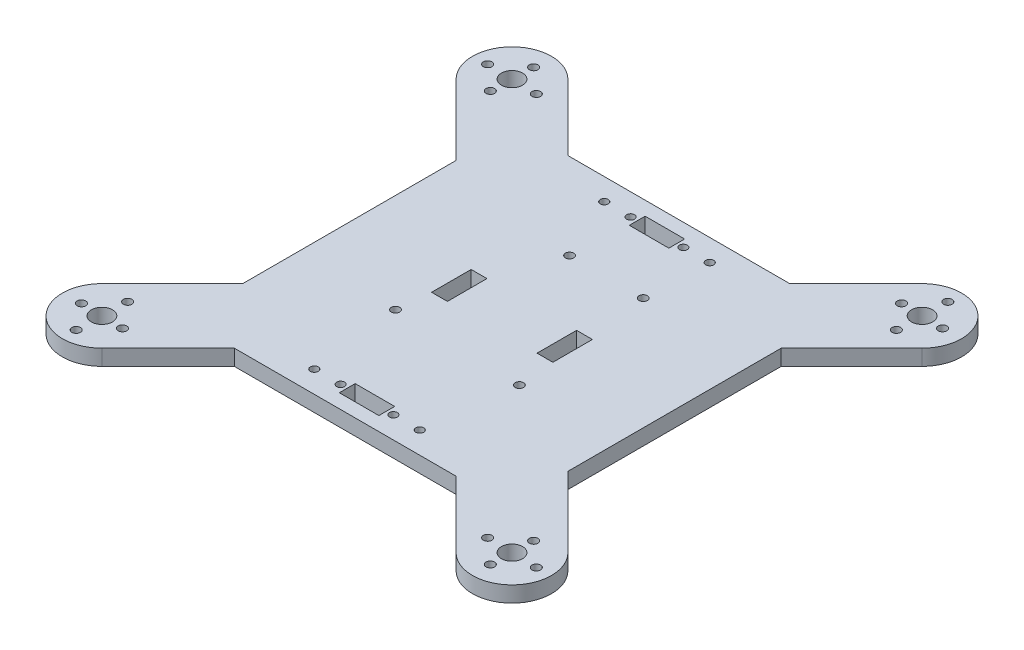
SolidWorks part; units mm, degrees
ref_plane "Front Plane" through (0, 0, 0) normal (0, 0, 1) x (1, 0, 0)
ref_plane "Top Plane" through (0, 0, 0) normal (0, 1, 0) x (1, 0, 0)
ref_plane "Right Plane" through (0, 0, 0) normal (1, 0, 0) x (0, 0, -1)
sketch "Sketch1" plane through (0, 0, 0) normal (0, 1, 0) x (1, 0, 0)
  line L0 (-67.1751, 88.3883) -> (88.3883, -67.1751)
  line L1 (-77.7817, 77.7817) -> (77.7817, 77.7817) construction
  line L2 (-77.7817, 77.7817) -> (-77.7817, -77.7817) construction
  line L3 (-77.7817, -77.7817) -> (77.7817, -77.7817) construction
  line L4 (77.7817, 77.7817) -> (77.7817, -77.7817) construction
  line L5 (-77.7817, 77.7817) -> (77.7817, -77.7817) construction
  line L6 (-77.7817, -77.7817) -> (77.7817, 77.7817) construction
  line L7 (67.1751, 88.3883) -> (-88.3883, -67.1751)
  line L8 (88.3883, 67.1751) -> (-67.1751, -88.3883)
  line L9 (-88.3883, 67.1751) -> (67.1751, -88.3883)
  line L10 (0, -1000) -> (0, 49000) construction
  line L11 (-1000, 0) -> (49000, 0) construction
  circle A0 centre (-77.7817, 77.7817) radius 15
  circle A1 centre (77.7817, 77.7817) radius 15
  circle A2 centre (-77.7817, -77.7817) radius 15
  circle A3 centre (77.7817, -77.7817) radius 15
  circle A4 centre (-77.7817, 77.7817) radius 4
  circle A5 centre (77.7817, 77.7817) radius 4
  circle A6 centre (77.7817, -77.7817) radius 4
  circle A7 centre (-77.7817, -77.7817) radius 4
  point P0 (0, 0)
  point P14 (10.6066, 10.6066)
  point P16 (10.6066, -10.6066)
  dimension "D4" = 8
  dimension "D1" = 220
  dimension "D2" = 30
  dimension "D3" = 30
extrude "Boss-Extrude1" add sketch "Sketch1" along normal blind 6 contours A0 A4 | A0 L9 L7 L0 | A2 A7 | L7 A2 L8 L9 | A3 L0 L8 L9 | L8 A1 L7 L0 | L7 L9 L8 L0 | A3 A6 | A1 A5 region at (-40.0766, 0, -40.0766) region at (-64.3155, 0, -83.3596) region at (40.0766, 0, -40.0766) region at (0, 0, 0) region at (40.0766, 0, 40.0766) region at (83.3596, 0, -91.248) region at (-40.0766, 0, 40.0766) region at (91.248, 0, 72.2039) region at (-72.2039, 0, 64.3155)
sketch "Sketch5" plane through (0, 6, 0) normal (0, 1, 0) x (1, 0, 0)
  line L0 (26.67, -35.3069) -> (-26.67, -35.3069)
  line L1 (26.67, -35.3069) -> (26.67, 30.7331)
  line L2 (21.59, 33.2731) -> (-11.176, 33.2731)
  line L3 (-26.67, -35.3069) -> (-26.67, 30.7331)
  line L4 (-26.67, 30.7331) -> (-13.716, 30.7331)
  line L5 (-13.716, 30.7331) -> (-11.176, 33.2731)
  line L6 (21.59, 33.2731) -> (24.13, 30.7331)
  line L7 (24.13, 30.7331) -> (26.67, 30.7331)
  line L8 (0, -1000) -> (0, 49000) construction
  line L10 (-1000, 0) -> (49000, 0) construction
  circle A0 centre (19.05, 30.7331) radius 1.5875
  circle A1 centre (-8.89, 30.7331) radius 1.5875
  circle A2 centre (24.13, -21.3369) radius 1.5875
  circle A3 centre (-24.13, -20.0669) radius 1.5875
  point P20 (0, -35.3069)
  line M10 (0, 21.2132) -> (-67.1751, 88.3883)
  line M12 (-88.3883, 67.1751) -> (-21.2132, 0)
  line M13 (-21.2132, 0) -> (-88.3883, -67.1751)
  line M15 (-67.1751, -88.3883) -> (0, -21.2132)
  line M16 (0, -21.2132) -> (67.1751, -88.3883)
  line M18 (88.3883, -67.1751) -> (21.2132, 0)
  line M19 (21.2132, 0) -> (88.3883, 67.1751)
  line M21 (67.1751, 88.3883) -> (0, 21.2132)
  dimension "D5" = 3.175
  dimension "D1" = 2.54
  dimension "D2" = 45
  dimension "D3" = 40.386
  dimension "D4" = 45
  dimension "D6" = 35.56
  dimension "D7" = 7.62
  dimension "D8" = 2.54
  dimension "D9" = 50.8
  dimension "D10" = 13.97
  dimension "D11" = 15.24
  dimension "D12" = 53.34
  dimension "D13" = 66.04
  dimension "D14" = 3.5921
  dimension "D15" = 2.54
  dimension "D16" = 2.54
  dimension "D17" = 2.54
  dimension "D18" = 32.766
  dimension "D19" = 66.04
  dimension "D20" = 12.954
extrude "Boss-Extrude2" add sketch "Sketch5" against normal blind 6 contours A1 M10 | A1 L5 L4 L3 L0 L1 L7 L6 L2 A3 A2 A0 M10 M12 M13 M15 M16 M18 M19 M21 | L3 M13 M12 | L1 M18 M19 | L0 M16 M15 | A1 L2 L5 M10 M21 region at (0.1063, 6, 1.0525) region at (0, 6, 30.609) region at (24.8511, 6, 0) region at (-24.8511, 6, 0) region at (0.3445, 6, -29.1791) region at (-8.5785, 6, -31.0446)
extrude "Cut-Extrude1" cut sketch "Sketch5<3>" against normal through all contours A1 | A0 | A2 | A3
sketch "Sketch5<3>" plane through (0, 6, 0) normal (0, 1, 0) x (1, 0, 0) same geometry as "Sketch5"
sketch "Sketch6" plane through (0, 6, 0) normal (0, 1, 0) x (1, 0, 0)
  line L0 (-1000, 0) -> (49000, 0) construction
  line L1 (0, -1000) -> (0, 49000) construction
  line L2 (0, 0) -> (-35355.3391, 35355.3391) construction
  line L3 (0, 0) -> (35355.3391, 35355.3391) construction
  line L4 (-77.5182, -68.2854) -> (-78.0453, -87.2781) construction
  line L5 (-69.7848, -78.0037) -> (-85.7787, -77.5598) construction
  circle A4 centre (-69.7848, -78.0037) radius 1.625
  circle A5 centre (-78.0453, -87.2781) radius 1.625
  circle A6 centre (-77.5182, -68.2854) radius 1.625
  circle A7 centre (-85.7787, -77.5598) radius 1.625
  circle A28 centre (-77.7817, -77.7817) radius 4 construction
  circle A29 centre (-77.7817, -77.7817) radius 4
  circle A30 centre (68.2854, -77.5182) radius 1.625
  circle A31 centre (87.2781, -78.0453) radius 1.625
  circle A32 centre (78.0037, -69.7848) radius 1.625
  circle A33 centre (77.5598, -85.7787) radius 1.625
  circle A38 centre (-87.2781, 78.0453) radius 1.625
  circle A39 centre (-77.5598, 85.7787) radius 1.625
  circle A40 centre (-78.0037, 69.7848) radius 1.625
  circle A41 centre (-68.2854, 77.5182) radius 1.625
  circle A42 centre (78.0453, 87.2781) radius 1.625
  circle A43 centre (77.5182, 68.2854) radius 1.625
  circle A44 centre (85.7787, 77.5598) radius 1.625
  circle A45 centre (69.7848, 78.0037) radius 1.625
  dimension "D1" = 18.9927
  dimension "D2" = 15.9938
  dimension "D3" = 9.7183
  dimension "D4" = 12.4197
  dimension "D5" = 12.4197
  dimension "D6" = 12.4197
extrude "Cut-Extrude2" cut sketch "Sketch6" against normal up to next (6 mm away)
sketch "Sketch7" plane through (0, 6, 0) normal (0, 1, 0) x (1, 0, 0)
  line L0 (88.3883, 67.1751) -> (26.67, 5.4568) construction
  line L1 (26.67, -5.4568) -> (26.67, 5.4568) construction
  line L2 (26.67, -5.4568) -> (88.3883, -67.1751) construction
  line L3 (-26.67, -5.4568) -> (-88.3883, -67.1751) construction
  line L4 (-88.3883, 67.1751) -> (-26.67, 5.4568) construction
  line L5 (-26.67, -5.4568) -> (-26.67, 5.4568) construction
  line L6 (88.3883, 67.1751) -> (26.67, 5.4568)
  line L7 (26.67, -5.4568) -> (26.67, 5.4568)
  line L8 (26.67, -5.4568) -> (88.3883, -67.1751)
  line L9 (-26.67, -5.4568) -> (-88.3883, -67.1751)
  line L10 (-88.3883, 67.1751) -> (-26.67, 5.4568)
  line L11 (-26.67, -5.4568) -> (-26.67, 5.4568)
  line L12 (-61.67, 40.4568) -> (-61.67, -40.4568)
  line L13 (0, -1000) -> (0, 49000) construction
  line L14 (61.67, 40.4568) -> (61.67, -40.4568)
  line L15 (-11.6179, 32.8311) -> (-11.176, 33.2731) construction
  line L16 (67.1751, 88.3883) -> (12.0599, 33.2731) construction
  line L17 (12.0599, 33.2731) -> (-11.176, 33.2731) construction
  line L18 (-67.1751, 88.3883) -> (-11.6179, 32.8311) construction
  line L19 (-11.6179, 32.8311) -> (-11.176, 33.2731)
  line L20 (67.1751, 88.3883) -> (12.0599, 33.2731)
  line L21 (12.0599, 33.2731) -> (-11.176, 33.2731)
  line L22 (-67.1751, 88.3883) -> (-11.6179, 32.8311)
  line L23 (14.0937, -35.3069) -> (67.1751, -88.3883) construction
  line L24 (14.0937, -35.3069) -> (-14.0937, -35.3069) construction
  line L25 (-14.0937, -35.3069) -> (-67.1751, -88.3883) construction
  line L26 (14.0937, -35.3069) -> (67.1751, -88.3883)
  line L27 (14.0937, -35.3069) -> (-14.0937, -35.3069)
  line L28 (-14.0937, -35.3069) -> (-67.1751, -88.3883)
  line L29 (-1000, 0) -> (49000, 0) construction
  line L30 (-42.0599, 63.2731) -> (42.0599, 63.2731)
  line L31 (-42.0599, -63.2731) -> (42.0599, -63.2731)
  line M25 (-14.0937, -35.3069) -> (14.0937, -35.3069)
  line M26 (14.0937, -35.3069) -> (67.1751, -88.3883)
  line M29 (26.67, -5.4568) -> (26.67, 5.4568)
  line M30 (26.67, 5.4568) -> (88.3883, 67.1751)
  line M33 (12.0599, 33.2731) -> (-11.176, 33.2731)
  line M34 (-11.176, 33.2731) -> (-11.6179, 32.8311)
  line M35 (-11.6179, 32.8311) -> (-67.1751, 88.3883)
  line M38 (-26.67, 5.4568) -> (-26.67, -5.4568)
  line M39 (-26.67, -5.4568) -> (-88.3883, -67.1751)
  dimension "D1" = 35
  dimension "D2" = 30
extrude "Boss-Extrude3" add sketch "Sketch7" against normal blind 6 contours L14 L8 M30 M29 | L10 L12 M39 M38 | L28 L31 M26 M25 | L30 L20 M35 M34 M33 region at (48.6168, 6, 0) region at (-48.6168, 6, 0) region at (-0.0014, 6, -51.0425) region at (0, 6, 51.6113)
sketch "Sketch8" plane through (0, 6, 0) normal (0, 1, 0) x (1, 0, 0)
  line L0 (0, -1000) -> (0, 49000) construction
  line L1 (-1000, 0) -> (49000, 0) construction
  line L2 (-20, 55) -> (20, 55) construction
  line L3 (-20, -55) -> (-20, 55) construction
  line L4 (-20, -55) -> (20, -55) construction
  line L5 (20, 55) -> (20, -55) construction
  line L6 (-7.5, -52) -> (7.5, -58) construction
  line L7 (-7.5, 58) -> (7.5, 58)
  line L8 (-7.5, 58) -> (-7.5, 52)
  line L9 (-7.5, 52) -> (7.5, 52)
  line L10 (7.5, 58) -> (7.5, 52)
  line L11 (-7.5, 58) -> (7.5, 52) construction
  line L12 (-7.5, 52) -> (7.5, 58) construction
  line L13 (-7.5, -58) -> (7.5, -52) construction
  line L14 (7.5, -58) -> (7.5, -52)
  line L15 (-7.5, -52) -> (7.5, -52)
  line L16 (-7.5, -58) -> (-7.5, -52)
  line L17 (-7.5, -58) -> (7.5, -58)
  line L18 (23, -7.5) -> (17, 7.5) construction
  line L19 (-23, 7.5) -> (-17, 7.5)
  line L20 (-23, 7.5) -> (-23, -7.5)
  line L21 (-23, -7.5) -> (-17, -7.5)
  line L22 (-17, 7.5) -> (-17, -7.5)
  line L23 (-23, 7.5) -> (-17, -7.5) construction
  line L24 (-23, -7.5) -> (-17, 7.5) construction
  line L25 (23, 7.5) -> (17, -7.5) construction
  line L26 (17, 7.5) -> (17, -7.5)
  line L27 (23, -7.5) -> (17, -7.5)
  line L28 (23, 7.5) -> (23, -7.5)
  line L29 (23, 7.5) -> (17, 7.5)
  circle A0 centre (-20, 55) radius 1.5
  circle A1 centre (20, 55) radius 1.5
  circle A2 centre (20, -55) radius 1.5
  circle A3 centre (-20, -55) radius 1.5
  circle A4 centre (-10, 55) radius 1.5
  circle A5 centre (10, 55) radius 1.5
  circle A6 centre (-10, -55) radius 1.5
  circle A7 centre (10, -55) radius 1.5
  point P15 (0, 55)
  point P26 (0, 0)
  point P32 (0, -55)
  point P33 (-20, 0)
  point P41 (20, 0)
  dimension "D3" = 3
  dimension "D4" = 3
  dimension "D5" = 3
  dimension "D6" = 3
  dimension "D8" = 3
  dimension "D1" = 40
  dimension "D2" = 110
  dimension "D7" = 10
  dimension "D9" = 6
  dimension "D10" = 15
  dimension "D11" = 6
  dimension "D12" = 15
extrude "Cut-Extrude7" cut sketch "Sketch8" along normal blind 6 and the other way through all
equation "\"Frame_Size\" = 220"
equation "\"Arm_Width\" = 30"
equation "\"Motor_Mount_Hole_Diameter\" = 8"
equation "\"Motor_Shaft_Diameter\" = 3"
equation "\"D1@Sketch1\"=\"Frame_Size\""
equation "\"D2@Sketch1\"=\"Arm_Width\""
equation "\"D3@Sketch1\"=\"Arm_Width\""
equation "\"D4@Sketch1\"=\"Motor_Mount_Hole_Diameter\""
equation "\"Frame_Thickness\" = 6"
equation "\"D1@Boss-Extrude1\"=\"Frame_Thickness\""
equation "\"D1@Boss-Extrude2\"=\"Frame_Thickness\""
equation "\"D1@Boss-Extrude3\"=\"Frame_Thickness\""
equation "\"Screw_Nut_Diameter\" = 6.5"
equation "\"Screw_Diameter\" = 3"
equation "\"Screw_Shaft_Length\" = 10"
equation "\"Screw_Hole_Separation_C2C\" = 20"
equation "\"Solder_Board_Small_Screw_Hole_Separation\" = 37"
equation "\"Solder_Board_Small_Screw_Hole_Diameter\" = 3.3"
equation "\"Solder_Board_Small_Length\" = 45.72"
equation "\"Solder_Board_Small_Width\" = 33.02"
equation "\"Solder_Board_Small_Thickness\" = 1.6"
equation "\"ESC_Length\" = 35"
equation "\"ESC_Width\" = 17"
equation "\"ESC_Thickness\" = 5"
equation "\"Battery_Length\" = 105"
equation "\"Battery_Width\" = 33"
equation "\"Battery_Thickness\" = 24"
equation "\"Battery_Holder_Screw_Hole_Distance_Long\" = 110"
equation "\"Battery_Holder_Screw_Hole_Distance_Short\" = 40"
equation "\"D1@Sketch8\"=\"Battery_Holder_Screw_Hole_Distance_Short\""
equation "\"D2@Sketch8\"=\"Battery_Holder_Screw_Hole_Distance_Long\""
equation "\"D3@Sketch8\"=\"Screw_Diameter\""
equation "\"D4@Sketch8\"=\"Screw_Diameter\""
equation "\"D5@Sketch8\"=\"Screw_Diameter\""
equation "\"D6@Sketch8\"=\"Screw_Diameter\""
equation "\"D8@Sketch8\"=\"Screw_Diameter\""
equation "\"D7@Sketch8\"=\"Battery_Holder_Screw_Hole_Distance_Short\"/4"
equation "\"D9@Sketch8\"=\"Frame_Thickness\""
equation "\"Screw_Nut_Thickness\" = 2.5"
equation "\"Tooth_Width\" = 15"
equation "\"D10@Sketch8\"=\"Tooth_Width\""
equation "\"D11@Sketch8\"=\"Frame_Thickness\""
equation "\"D12@Sketch8\"=\"Tooth_Width\""
